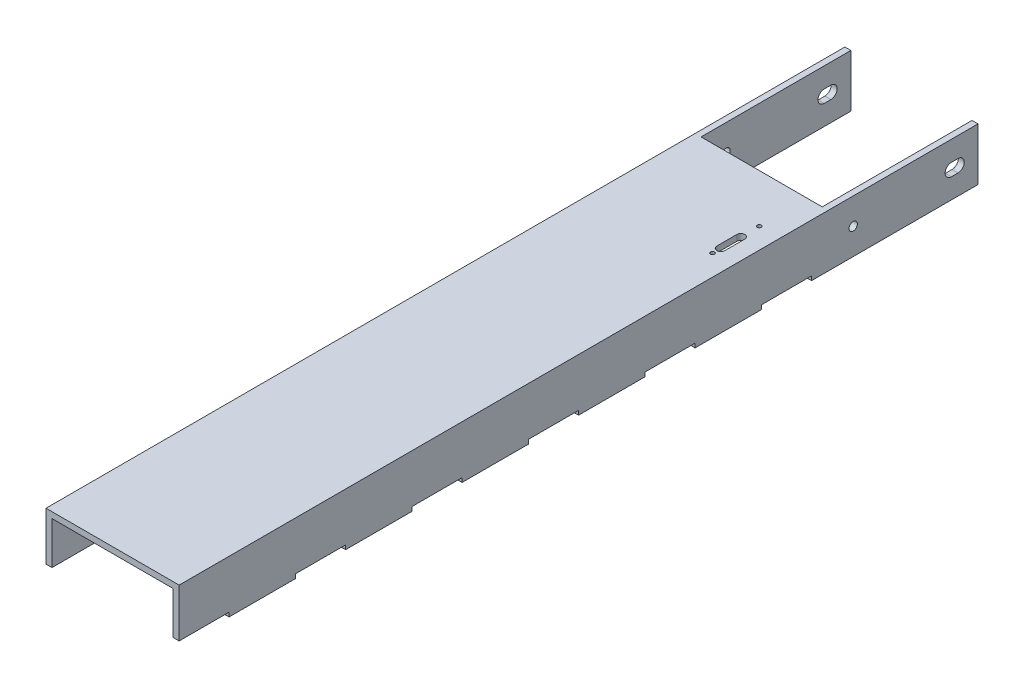
SolidWorks part; units mm, degrees
ref_plane "Front Plane" through (0, 0, 0) normal (0, 0, 1) x (1, 0, 0)
ref_plane "Top Plane" through (0, 0, 0) normal (0, 1, 0) x (1, 0, 0)
ref_plane "Right Plane" through (0, 0, 0) normal (1, 0, 0) x (0, 0, -1)
sketch "Sketch1" plane through (0, 0, 0) normal (0, 0, 1) x (1, 0, 0)
  line L0 (-50.8, 0) -> (50.8, 0)
  line L1 (50.8, 0) -> (50.8, -40.132)
  line L2 (50.8, -40.132) -> (46.228, -40.132)
  line L3 (46.228, -40.132) -> (46.228, -4.572)
  line L4 (46.228, -4.572) -> (-46.228, -4.572)
  line L5 (-46.228, -4.572) -> (-46.228, -40.132)
  line L6 (-46.228, -40.132) -> (-50.8, -40.132)
  line L7 (-50.8, -40.132) -> (-50.8, 0)
  point P8 (0, 0)
  dimension "D1" = 40.132
  dimension "D2" = 4.572
  dimension "D3" = 4.572
  dimension "D4" = 101.6
extrude "Boss-Extrude1" add sketch "Sketch1" along normal blind 609.6
sketch "Sketch3" plane through (0, 0, 0) normal (0, 1, 0) x (1, 0, 0)
  line L0 (50.8, 0) -> (-50.8, 0) construction
  line L1 (-46.228, -114.3) -> (46.228, -114.3)
  line L2 (-46.228, -114.3) -> (-46.228, 0)
  line L3 (-46.228, 0) -> (46.228, 0)
  line L4 (46.228, -114.3) -> (46.228, 0)
  line L5 (-46.228, -114.3) -> (46.228, 0) construction
  line L6 (-46.228, 0) -> (46.228, -114.3) construction
  line L7 (-46.228, -609.6) -> (-46.228, 0) construction
  line L8 (46.228, -609.6) -> (46.228, 0) construction
  line L9 (34.925, -165.1) -> (34.925, -180.34) construction
  line L10 (37.973, -165.1) -> (37.973, -180.34)
  line L11 (31.877, -165.1) -> (31.877, -180.34)
  arc A0 (37.973, -165.1) -> (31.877, -165.1) centre (34.925, -165.1) ccw
  arc A1 (31.877, -180.34) -> (37.973, -180.34) centre (34.925, -180.34) ccw
  circle A2 centre (34.925, -151.13) radius 1.524
  circle A3 centre (34.925, -186.69) radius 1.524
  point P0 (0, -57.15)
  point P13 (34.925, -172.72)
  dimension "D2" = 6.096
  dimension "D6" = 3.048
  dimension "D1" = 114.3
  dimension "D3" = 15.24
  dimension "D4" = 50.8
  dimension "D5" = 8.255
  dimension "D7" = 13.97
  dimension "D8" = 6.35
extrude "Cut-Extrude1" cut sketch "Sketch3" against normal through all
sketch "Sketch4" plane through (50.8, 0, 0) normal (1, 0, 0) x (0, 0, -1)
  line L0 (-15.24, -20.066) -> (-20.32, -20.066) construction
  line L1 (-15.24, -24.8285) -> (-20.32, -24.8285)
  line L2 (-15.24, -15.3035) -> (-20.32, -15.3035)
  line L3 (0, -40.132) -> (0, 0) construction
  line L4 (-520.7, -40.132) -> (-482.6, -40.132)
  line L5 (-609.6, -40.132) -> (-571.5, -40.132)
  line L6 (-609.6, -40.132) -> (-609.6, -36.957)
  line L7 (-609.6, -36.957) -> (-571.5, -36.957)
  line L8 (-571.5, -40.132) -> (-571.5, -36.957)
  line L9 (-520.7, -40.132) -> (-520.7, -36.957)
  line L10 (-520.7, -36.957) -> (-482.6, -36.957)
  line L11 (-482.6, -40.132) -> (-482.6, -36.957)
  line L12 (-431.8, -40.132) -> (-393.7, -40.132)
  line L13 (-431.8, -40.132) -> (-431.8, -36.957)
  line L14 (-431.8, -36.957) -> (-393.7, -36.957)
  line L15 (-393.7, -40.132) -> (-393.7, -36.957)
  line L16 (-342.9, -40.132) -> (-304.8, -40.132)
  line L17 (-342.9, -40.132) -> (-342.9, -36.957)
  line L18 (-342.9, -36.957) -> (-304.8, -36.957)
  line L19 (-304.8, -40.132) -> (-304.8, -36.957)
  line L20 (-254, -40.132) -> (-215.9, -40.132)
  line L21 (-254, -40.132) -> (-254, -36.957)
  line L22 (-254, -36.957) -> (-215.9, -36.957)
  line L23 (-215.9, -40.132) -> (-215.9, -36.957)
  line L24 (-165.1, -40.132) -> (-127, -40.132)
  line L25 (-165.1, -40.132) -> (-165.1, -36.957)
  line L26 (-165.1, -36.957) -> (-127, -36.957)
  line L27 (-127, -40.132) -> (-127, -36.957)
  arc A0 (-15.24, -24.8285) -> (-15.24, -15.3035) centre (-15.24, -20.066) ccw
  arc A1 (-20.32, -15.3035) -> (-20.32, -24.8285) centre (-20.32, -20.066) ccw
  circle A2 centre (-95.25, -20.066) radius 3.175
  point P3 (-17.78, -20.066)
  point P10 (0, -20.066)
  dimension "D3" = 9.525
  dimension "D5" = 6.35
  dimension "D1" = 5.08
  dimension "D2" = 15.24
  dimension "D4" = 95.25
  dimension "D6" = 3.175
  dimension "D7" = 38.1
  dimension "D8" = 6
extrude "Cut-Extrude2" cut sketch "Sketch4" against normal through all
